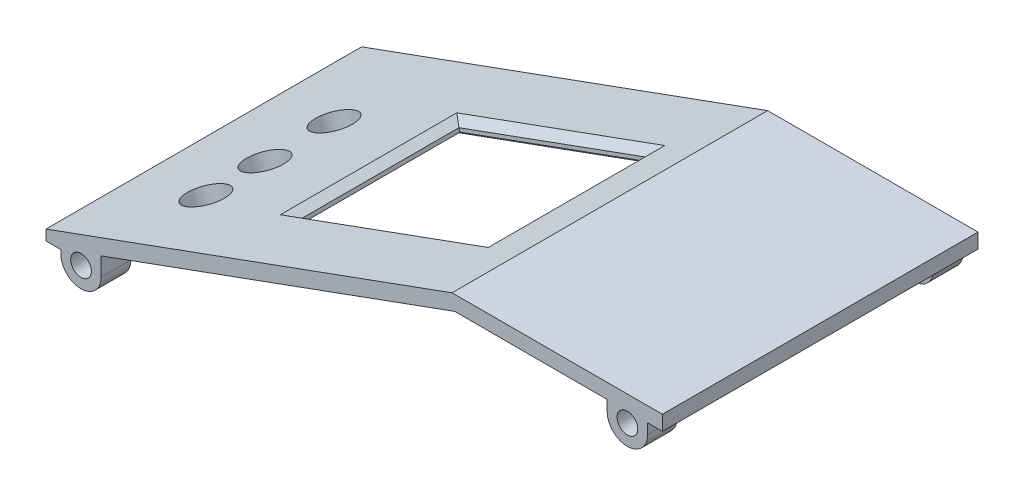
SolidWorks part; units mm, degrees
ref_plane "Спереди" through (0, 0, 0) normal (0, 0, 1) x (1, 0, 0)
ref_plane "Сверху" through (0, 0, 0) normal (0, 1, 0) x (1, 0, 0)
ref_plane "Справа" through (0, 0, 0) normal (1, 0, 0) x (0, 0, -1)
sketch "Эскиз1" plane through (0, 0, 0) normal (0, 0, 1) x (1, 0, 0)
  line L0 (11.6239, 71) -> (10.5978, 73.8191) construction
  line L1 (53.75, 74) -> (11.0949, 74)
  line L2 (11.0949, 74) -> (-71.25, 44.0289)
  line L3 (-71.25, 44.0289) -> (-71.25, 41.9283)
  line L4 (-71.25, 41.9283) -> (-68.25, 41.9283)
  line L5 (-68.25, 41.9283) -> (11.6239, 71)
  line L6 (11.6239, 71) -> (53.75, 71)
  line L7 (53.75, 71) -> (53.75, 74)
  line L8 (-68.25, 41.9283) -> (-69.2761, 44.7474) construction
  line L10 (53.75, -6) -> (53.75, 71) construction
  line L11 (53.75, 71) -> (50.75, 71) construction
  line L12 (-71.25, 41.9283) -> (-71.25, -6) construction
  dimension "D1" = 3
  dimension "D2" = 20
  dimension "D3" = 85
extrude "Бобышка-Вытянуть1" add sketch "Эскиз1" along normal mid plane 64
sketch "Эскиз2" plane through (0, 0, 0) normal (0, 0, 1) x (1, 0, 0)
  line L2 (42.55, 74) -> (42.55, 68.9)
  line L4 (50.75, 71) -> (50.75, 3.2) construction
  line L5 (50.75, 68.9) -> (50.75, 74)
  line L6 (53.75, 74) -> (11.0949, 74) construction
  line L7 (50.75, 74) -> (42.55, 74)
  line L9 (-60.05, 48.1054) -> (-60.05, 41.1858)
  line L10 (11.0949, 74) -> (-71.25, 44.0289) construction
  line L11 (-68.25, -3) -> (-68.25, 41.9283) construction
  line L12 (-68.25, 41.1858) -> (-68.25, 45.1208)
  line L13 (-68.25, 45.1208) -> (-60.05, 48.1054)
  arc A0 (42.55, 68.9) -> (50.75, 68.9) centre (46.65, 68.9) ccw
  circle A1 centre (46.65, 68.9) radius 2.1
  arc A2 (-60.05, 41.1858) -> (-68.25, 41.1858) centre (-64.15, 41.1858) cw
  circle A3 centre (-64.15, 41.1858) radius 2.1
  dimension "D1" = 4.2
  dimension "D2" = 2
  dimension "D3" = 3
  dimension "D4" = 2
  dimension "D5" = 3
extrude "Бобышка-Вытянуть2" add sketch "Эскиз2" against normal blind 6 from surface contours L2 A0 L5 L7 A1 | A1 | A2 L9 L13 L12 A3 | A3 region at (46.65, 73.8768, 0) region at (-60.1874, 44.6456, 0) region at (46.65, 68.9, 0) region at (-64.15, 41.1858, 0) starting at face at (-11.5045, 59.6979, 32)
extrude "Бобышка-Вытянуть3" add sketch "Эскиз2<3>" along normal blind 6 from surface contours A1 | L2 A0 L5 L7 A1 | A2 L9 L13 L12 A3 | A3 region at (46.65, 73.8768, 0) region at (-60.1874, 44.6456, 0) region at (46.65, 68.9, 0) region at (-64.15, 41.1858, 0) starting at face at (-11.5045, 59.6979, -32)
sketch "Эскиз2<3>" plane through (0, 0, 0) normal (0, 0, 1) x (1, 0, 0) same geometry as "Эскиз2"
extrude "Вырез-Вытянуть1" cut sketch "Эскиз2<4>" against normal blind 4 from surface contours A1 | A3 region at (46.65, 68.9, 0) region at (-64.15, 41.1858, 0) starting at face at (-5.8772, 58.3407, 32)
sketch "Эскиз2<4>" plane through (0, 0, 0) normal (0, 0, 1) x (1, 0, 0) same geometry as "Эскиз2"
extrude "Вырез-Вытянуть2" cut sketch "Эскиз2<5>" along normal blind 4 from surface contours A1 | A3 region at (46.65, 68.9, 0) region at (-64.15, 41.1858, 0) starting at face at (-5.8772, 58.3407, -32)
sketch "Эскиз2<5>" plane through (0, 0, 0) normal (0, 0, 1) x (1, 0, 0) same geometry as "Эскиз2"
sketch "Эскиз3" plane through (-21.4592, 58.9587, 0) normal (0.342, -0.9397, 0) x (0.9397, 0.342, 0)
  line L8 (-20.0437, -17.5) -> (-20.0437, -14.8)
  line L9 (28.1563, -17.5) -> (-20.0437, -17.5)
  line L10 (28.1563, 17.5) -> (28.1563, -17.5)
  line L11 (-19.8437, 17.5) -> (28.1563, 17.5)
  line L12 (-20.0437, -17.5) -> (-20.0437, 17.5)
  line L13 (28.1563, -17.5) -> (-20.0437, -17.5)
  line L14 (28.1563, 17.5) -> (28.1563, -17.5)
  line L15 (-20.0437, 17.5) -> (28.1563, 17.5)
  dimension "D1" = 0.2
extrude "Вырез-Вытянуть3" cut sketch "Эскиз3" against normal blind 0.8
sketch "Эскиз4" plane through (-21.4592, 58.9587, 0) normal (0.342, -0.9397, 0) x (0.9397, 0.342, 0)
  line L16 (-14.8437, -16.4) -> (27.0563, -16.4)
  line L17 (-14.8437, 16.4) -> (-14.8437, -16.4)
  line L18 (27.0563, 16.4) -> (-14.8437, 16.4)
  line L19 (27.0563, -16.4) -> (27.0563, 16.4)
  line L20 (-14.8437, -16.4) -> (27.0563, -16.4)
  line L21 (-14.8437, 16.4) -> (-14.8437, -16.4)
  line L22 (27.0563, 16.4) -> (-14.8437, 16.4)
  line L23 (27.0563, -16.4) -> (27.0563, 16.4)
  dimension "D1" = 0.5
extrude "Вырез-Вытянуть4" cut sketch "Эскиз4" against normal through all
sketch "Эскиз7" plane through (-22.4853, 61.7778, 0) normal (-0.342, 0.9397, 0) x (0.9397, 0.342, 0)
  circle A2 centre (-34.6937, 10.25) radius 4
  circle A3 centre (-34.6937, 10.25) radius 4
  circle A20 centre (-34.6787, -3.75) radius 4
  circle A21 centre (-34.6787, -15.75) radius 4
  dimension "D2" = 8
  dimension "D1" = 0.5
extrude "Вырез-Вытянуть5" cut sketch "Эскиз7" against normal blind 10
sketch "Эскиз8" plane through (-21.4592, 58.9587, 0) normal (0.342, -0.9397, 0) x (0.9397, 0.342, 0)
  line L0 (28.1563, -17.5) -> (28.1563, 17.5) construction
  circle A1 centre (30.7063, 15) radius 2.55
  circle A4 centre (30.7063, -15) radius 2.55
  circle A7 centre (-46.2937, -16.5) radius 2.55
  circle A8 centre (-46.2937, 16.5) radius 2.55
extrude "Бобышка-Вытянуть4" add sketch "Эскиз8" along normal up to surface (2 mm away)
sketch "Эскиз9" plane through (-20.7752, 57.0794, 0) normal (0.342, -0.9397, 0) x (0.9397, 0.342, 0)
  circle A0 centre (30.7063, -15) radius 1.4
  circle A1 centre (30.7063, 15) radius 1.4
  circle A2 centre (-46.2937, -16.5) radius 1.4
  circle A3 centre (-46.2937, 16.5) radius 1.4
  dimension "D1" = 2.8
extrude "Вырез-Вытянуть6" cut sketch "Эскиз9" against normal blind 3
chamfer "Фаска1" distance 1.5 angle 45 4 edges at (2.9393, 71.0316, 0) (-16.7472, 63.8663, -16.4) (-36.4338, 56.701, 0) (-16.7472, 63.8663, 16.4)
